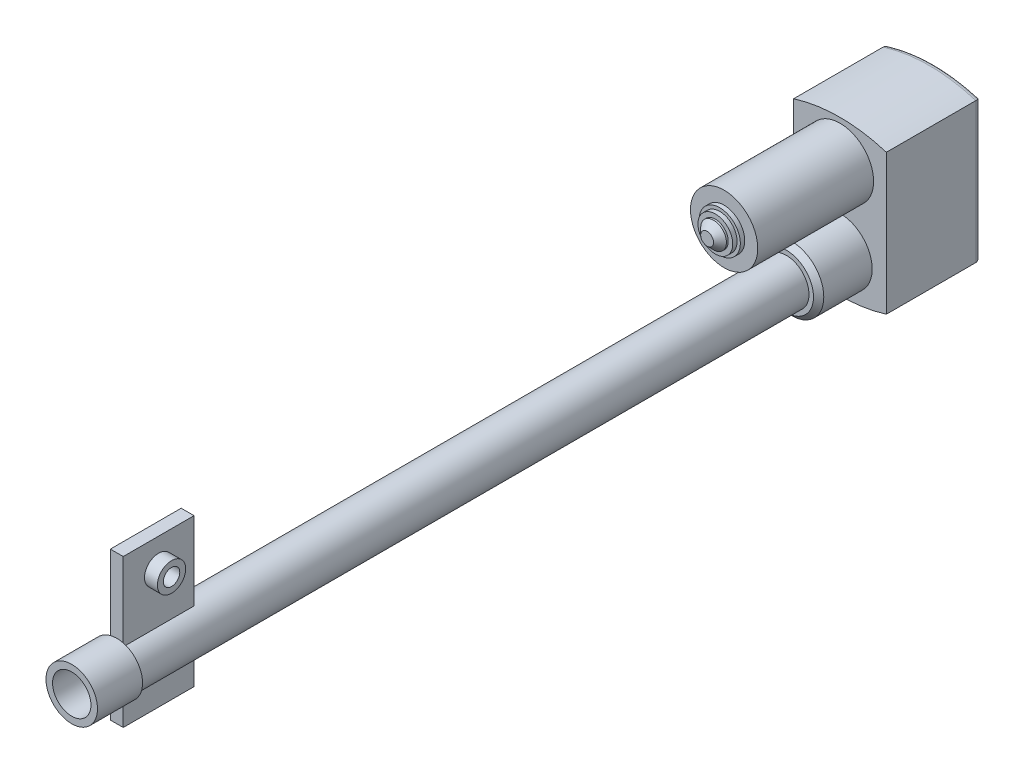
SolidWorks part; units mm, degrees
ref_plane "Alzado" through (0, 0, 0) normal (0, 0, 1) x (1, 0, 0)
ref_plane "Planta" through (0, 0, 0) normal (0, 1, 0) x (1, 0, 0)
ref_plane "Vista lateral" through (0, 0, 0) normal (1, 0, 0) x (0, 0, -1)
sketch "Croquis1" plane through (0, 0, 0) normal (1, 0, 0) x (0, 0, -1)
  line L1 (-36.75, -60) -> (36.75, -60)
  line L2 (-36.75, -60) -> (-36.75, 60)
  line L3 (-36.75, 60) -> (36.75, 60)
  line L4 (36.75, -60) -> (36.75, 60)
  line L5 (-36.75, -60) -> (36.75, 60) construction
  line L6 (-36.75, 60) -> (36.75, -60) construction
  point P0 (0, 0)
extrude "Saliente-Extruir1" add sketch "Croquis1" along normal blind 72
sketch "Croquis2" plane through (0, 0, 36.75) normal (0, 0, 1) x (1, 0, 0)
  line L0 (36, 60) -> (36, 29.9) construction
  line L1 (72, 60) -> (0, 60) construction
  circle A0 centre (36, 29.9) radius 26.1
extrude "Saliente-Extruir2" add sketch "Croquis2" along normal blind 90
sketch "Croquis3" plane through (0, 0, 126.75) normal (0, 0, 1) x (1, 0, 0)
  line L0 (9.9, 29.9) -> (62.1, 29.9) construction
  circle A0 centre (36, 29.9) radius 26.1 construction
  circle A1 centre (36, 29.9) radius 26.1 construction
  circle A2 centre (36, 29.9) radius 16
extrude "Saliente-Extruir3" add sketch "Croquis3" along normal blind 3.4
sketch "Croquis4" plane through (0, 0, 130.15) normal (0, 0, 1) x (1, 0, 0)
  line L0 (20, 29.9) -> (52, 29.9) construction
  circle A0 centre (36, 29.9) radius 16 construction
  circle A1 centre (36, 29.9) radius 16 construction
  circle A2 centre (36, 29.9) radius 13.5
extrude "Saliente-Extruir4" add sketch "Croquis4" along normal blind 3.4
sketch "Croquis5" plane through (0, 0, 133.55) normal (0, 0, 1) x (1, 0, 0)
  line L0 (22.5, 29.9) -> (49.5, 29.9) construction
  circle A0 centre (36, 29.9) radius 13.5 construction
  circle A1 centre (36, 29.9) radius 10
extrude "Saliente-Extruir5" add sketch "Croquis5" along normal blind 6.4
fillet "Chaflán1" radius 5 1 edges at (46, 29.9, 139.95) type face fillet profile chamfer first side face at (46, 29.9, 139.95) second side face at (46, 29.9, 139.95)
sketch "Croquis6" plane through (0, 0, 36.75) normal (0, 0, 1) x (1, 0, 0)
  line L0 (36, -60) -> (36, -29.6) construction
  line L1 (72, -60) -> (0, -60) construction
  circle A0 centre (36, -29.6) radius 25
extrude "Saliente-Extruir6" add sketch "Croquis6" along normal blind 41.6
sketch "Croquis7" plane through (0, 0, 78.35) normal (0, 0, 1) x (1, 0, 0)
  line L0 (11, -29.6) -> (61, -29.6) construction
  circle A0 centre (36, -29.6) radius 25 construction
  circle A1 centre (36, -29.6) radius 17.5
extrude "Saliente-Extruir7" add sketch "Croquis7" along normal blind 520
fillet "Chaflán2" radius 4 1 edges at (61, -29.6, 78.35) type face fillet profile chamfer first side face at (61, -29.6, 78.35) second side face at (53.5, -29.6, 78.35)
sketch "Croquis8" plane through (0, 0, 598.35) normal (0, 0, 1) x (1, 0, 0)
  line L0 (18.5, -29.6) -> (53.5, -29.6) construction
  circle A0 centre (36, -29.6) radius 17.5 construction
  circle A1 centre (36, -29.6) radius 20
extrude "Saliente-Extruir8" add sketch "Croquis8" along normal blind 35
ref_plane "Plano1" through (36, 0, 0) normal (1, 0, 0) x (0, 0, -1)
sketch "Croquis11" plane through (36, 0, 0) normal (1, 0, 0) x (0, 0, -1)
  line L0 (-598.35, -12.1) -> (-543.35, -12.1) construction
  line L1 (-78.35, -12.1) -> (-598.35, -12.1) construction
  line L2 (-543.35, -12.1) -> (-543.35, 47.9) construction
  line L3 (-598.35, -47.1) -> (-598.35, -67.1) construction
  line L5 (-598.35, -67.1) -> (-543.35, -67.1)
  line L6 (-598.35, -67.1) -> (-598.35, 47.9)
  line L7 (-598.35, 47.9) -> (-543.35, 47.9)
  line L8 (-543.35, -67.1) -> (-543.35, 47.9)
extrude "Saliente-Extruir11" add sketch "Croquis11" along normal blind 5 and the other way blind 5
sketch "Croquis9" plane through (0, 0, 633.35) normal (0, 0, 1) x (1, 0, 0)
  line L0 (16, -29.6) -> (56, -29.6) construction
  circle A0 centre (36, -29.6) radius 20 construction
  circle A1 centre (36, -29.6) radius 14.9
extrude "Cortar-Extruir1" cut sketch "Croquis9" against normal blind 450
sketch "Croquis12" plane through (41, 0, 0) normal (1, 0, 0) x (0, 0, -1)
  line L0 (-598.35, 47.9) -> (-598.35, 2.9) construction
  line L1 (-598.35, 47.9) -> (-598.35, -10.2351) construction
  line L2 (-598.35, 2.9) -> (-543.35, 47.9) construction
  line L3 (-543.35, -12.8295) -> (-543.35, 47.9) construction
  circle A0 centre (-570.85, 25.4) radius 11
extrude "Saliente-Extruir12" add sketch "Croquis12" along normal blind 10 and the other way blind 20
sketch "Croquis13" plane through (51, 0, 0) normal (1, 0, 0) x (0, 0, -1)
  circle A0 centre (-570.85, 25.4) radius 6.4
extrude "Cortar-Extruir2" cut sketch "Croquis13" against normal blind 30
sketch "Croquis14" plane through (0, 0, -36.75) normal (0, 0, -1) x (-1, 0, 0)
  line L0 (-72, -60) -> (0, -60) construction
  circle A0 centre (-36, -60) radius 120
  circle A1 centre (-36, 60) radius 120
  line M3 (0, -60) -> (0, 60)
  line M4 (0, 60) -> (-72, 60)
  line M5 (-72, 60) -> (-72, -60)
  line M6 (-72, -60) -> (0, -60)
extrude "Cortar-Extruir4" cut sketch "Croquis14" against normal blind 91 contours A0 M3 M4 | A1 M6 M3 | A1 M5 M6 | A0 M4 M5 region at (8.958, 58.3486, -36.75) region at (8.958, -58.3486, -36.75) region at (63.042, 58.3486, -36.75) region at (63.042, -58.3486, -36.75)
fillet "Redondeo1" radius 4 4 edges at (0, 0, -36.75) (36, -60, -36.75) (72, 0, -36.75) (36, 60, -36.75)
